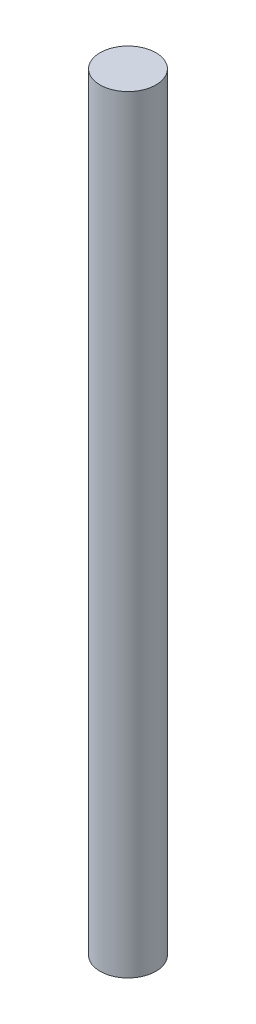
SolidWorks part; units mm, degrees
ref_plane "Спереди" through (0, 0, 0) normal (0, 0, 1) x (1, 0, 0)
ref_plane "Сверху" through (0, 0, 0) normal (0, 1, 0) x (1, 0, 0)
ref_plane "Справа" through (0, 0, 0) normal (1, 0, 0) x (0, 0, -1)
sketch "Эскиз1" plane through (0, 0, 0) normal (0, 1, 0) x (1, 0, 0)
  circle A0 centre (0, 0) radius 4
  dimension "D1" = 8
extrude "Бобышка-Вытянуть1" add sketch "Эскиз1" along normal blind 110
